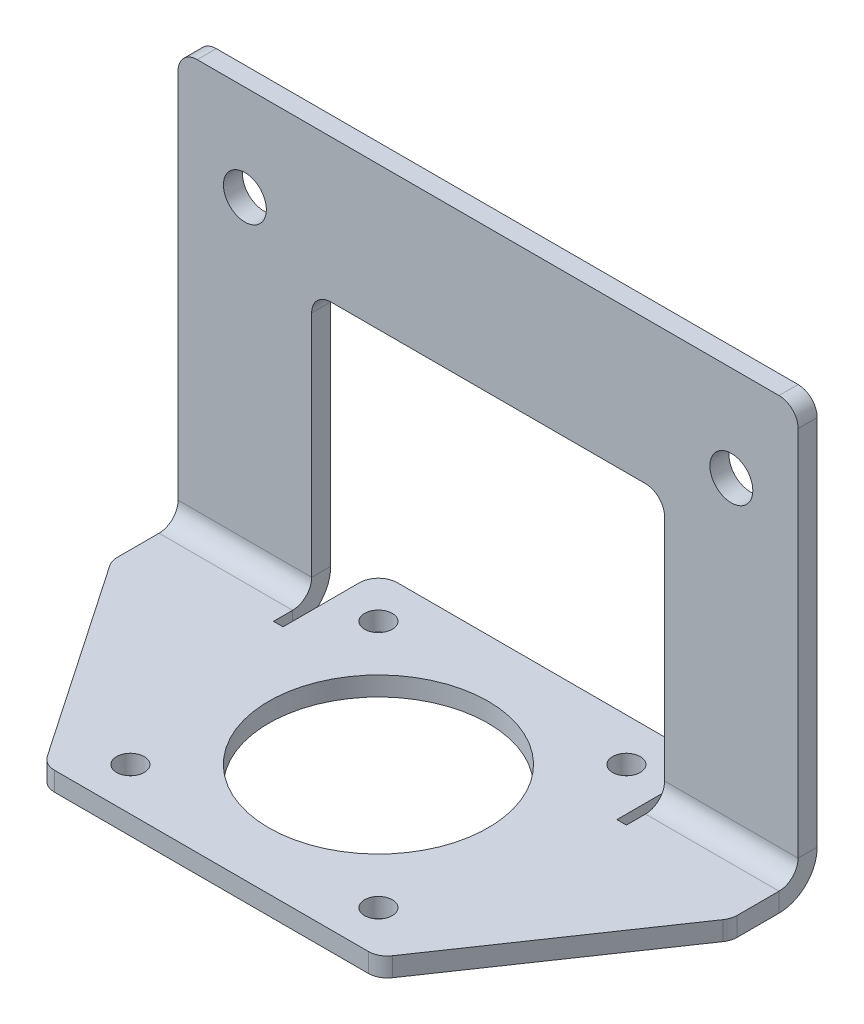
SolidWorks part; units mm, degrees
note: The reader was unsure of these and kept them because the rebuilt part matched: flange length of "Edge-Flange1".
material "Plain Carbon Steel"
ref_plane "Front Plane" through (0, 0, 0) normal (0, 0, 1) x (1, 0, 0)
ref_plane "Top Plane" through (0, 0, 0) normal (0, 1, 0) x (1, 0, 0)
ref_plane "Right Plane" through (0, 0, 0) normal (1, 0, 0) x (0, 0, -1)
sketch "Sketch1" plane through (0, 0, 0) normal (0, 1, 0) x (1, 0, 0)
  line L0 (-17.5, -17.5) -> (-32.5, -17.5)
  line L1 (-17.5, -17.5) -> (17.5, -17.5)
  line L2 (-17.5, 8.5) -> (-17.5, 17.5)
  line L3 (-17.5, 17.5) -> (17.5, 17.5)
  line L4 (17.5, 8.5) -> (17.5, 17.5)
  line L5 (-17.5, -17.5) -> (17.5, 17.5) construction
  line L6 (-17.5, 17.5) -> (17.5, -17.5) construction
  line L7 (-32.5, -17.5) -> (-32.5, 9.5)
  line L8 (-32.5, 9.5) -> (-18.5, 9.5)
  line L9 (0, 0) -> (0, 17.5) construction
  line L10 (17.5, -17.5) -> (32.5, -17.5)
  line L11 (32.5, -17.5) -> (32.5, 9.5)
  line L12 (32.5, 9.5) -> (18.5, 9.5)
  line L13 (-18.5, 9.5) -> (-18.5, 7.5)
  line L14 (-18.5, 7.5) -> (-17.5, 7.5)
  line L15 (-17.5, 7.5) -> (-17.5, 8.5)
  line L16 (17.5, 7.5) -> (17.5, 8.5)
  line L17 (18.5, 7.5) -> (17.5, 7.5)
  line L18 (18.5, 9.5) -> (18.5, 7.5)
  point P0 (0, 0)
  dimension "D1" = 35
  dimension "D2" = 15
  dimension "D3" = 9
  dimension "D4" = 17.5
  dimension "D5" = 17.5
  dimension "D6" = 2
  dimension "D7" = 1
  dimension "D8" = 8
base flange "Base-Flange1" sketch "Sketch1" thickness 2 reverse thickness direction no parameters "D1"=2
edge flange "Edge-Flange1" sketch "Sketch8" flange angle 90 flange length 45 flange position bend outside bend radius 2 thickness 2 relief rectangular parameters "D6"=10
sketch "Sketch8" plane through (0, 0, -9.5) normal (0, 0, -1) x (-1, 0, 0)
  line L0 (18.5, 0) -> (32.5, 0) construction
  line L1 (18.5, 0) -> (32.5, 0)
  line L2 (18.5, 0) -> (18.5, 43)
  line L3 (18.5, 43) -> (32.5, 43)
  line L4 (32.5, 43) -> (32.5, 0)
bend "EdgeBend1" bend radius 2 bend angle 90 parameters "D5"=1
mirror "Mirror1" about plane through (0, 0, 0) normal (1, 0, 0) of "Edge-Flange1"
bend "MirrorBend1" bend radius 2 bend angle 90 parameters "D5"=2
fillet "Fillet1" radius 2 2 edges at (17.5, -1, -17.5) (-17.5, -1, -17.5)
sketch "Sketch9" plane through (0, 0, -11.5) normal (0, 0, 1) x (1, 0, 0)
  line L0 (18.5, 43) -> (18.5, 2) construction
  line L1 (-18.5, 43) -> (18.5, 43)
  line L2 (-18.5, 43) -> (-18.5, 28)
  line L3 (-18.5, 28) -> (18.5, 28)
  line L4 (18.5, 43) -> (18.5, 28)
  line L5 (15.5, 0) -> (-15.5, 0) construction
  dimension "D1" = 28
extrude "Boss-Extrude1" add sketch "Sketch9" against normal blind 2
fillet "Fillet2" radius 2 4 edges at (-18.5, 28, -12.5) (18.5, 28, -12.5) (32.5, 43, -12.5) (-32.5, 43, -12.5)
sketch "Sketch10" plane through (0, 0, 0) normal (0, 1, 0) x (1, 0, 0)
  line L0 (-32.5, 4.5) -> (-17.5, -17.5)
  line L1 (-32.5, 9.5) -> (-32.5, -17.5) construction
  line L2 (-32.5, -17.5) -> (32.5, -17.5) construction
  line L3 (-17.5, -17.5) -> (-32.5, -17.5)
  line L4 (-32.5, -17.5) -> (-32.5, 4.5)
  dimension "D1" = 17.5
  dimension "D2" = 5
extrude "Cut-Extrude1" cut sketch "Sketch10" against normal blind 2 normal cut yes
mirror "Mirror2" about plane through (0, 0, 0) normal (1, 0, 0) of "Cut-Extrude1"
fillet "Fillet3" radius 2 4 edges at (-32.5, -1, -4.5) (-17.5, -1, 17.5) (17.5, -1, 17.5) (32.5, -1, -4.5)
hole_wizard "M2.5 Clearance Hole1" positions "Sketch11" profile "Sketch12" hole size "M2.5" standard "ISO" end condition through all
sketch "Sketch11" plane through (0, 0, 0) normal (0, 1, 0) x (1, 0, 0)
  point P0 (13, -13)
  point P3 (-13, -13)
  point P6 (-13, 13)
  point P9 (13, 13)
sketch "Sketch12" plane through (13, 0, 13) normal (1, 0, 0) x (0, 0, 1)
  line L0 (0, 0) -> (0, 2)
  line L1 (0, 2) -> (1.45, 2)
  line L2 (1.45, 2) -> (1.45, 0)
  line L5 (1.45, 0) -> (0, 0)
  line L11 (0, -6.35) -> (0, 107.95) construction
  dimension "Thru Hole Dia." = 2.9
  dimension "Thru Hole Depth" = 2
hole_wizard "M4 Clearance Hole1" positions "Sketch13" profile "Sketch14" hole size "M4" standard "ISO" end condition through all
sketch "Sketch13" plane through (0, 0, -11.5) normal (0, 0, 1) x (1, 0, 0)
  line L0 (-25.5, 33) -> (0, 33) construction
  line L1 (0, 33) -> (25.5, 33) construction
  line L3 (0, 33) -> (0, 43) construction
  line L4 (-30.5, 43) -> (30.5, 43) construction
  line L6 (0, 33) -> (0, 28) construction
  line L7 (-16.5, 28) -> (16.5, 28) construction
  line L9 (-32.5, 2) -> (-32.5, 41) construction
  point P0 (-25.5, 33)
  point P2 (25.5, 33)
  dimension "D1" = 7
  dimension "D2" = 10
sketch "Sketch14" plane through (-25.5, 33, -11.5) normal (1, 0, 0) x (0, -1, 0)
  line L0 (0, 0) -> (0, 6)
  line L1 (0, 6) -> (2.25, 6)
  line L2 (2.25, 6) -> (2.25, 0)
  line L5 (2.25, 0) -> (0, 0)
  line L11 (0, -6.35) -> (0, 107.95) construction
  dimension "Thru Hole Dia." = 4.5
  dimension "Thru Hole Depth" = 6
sketch "Sketch15" plane through (0, 0, 0) normal (0, 1, 0) x (1, 0, 0)
  circle A0 centre (0, 0) radius 11.5
  dimension "D1" = 23
extrude "Cut-Extrude2" cut sketch "Sketch15" against normal blind 10
sketch "Bend-Lines1" [suppressed] plane through (0, 0, 0) normal (0, 1, 0) x (1, 0, 0)
sketch "Bounding-Box1" [suppressed] plane through (0, 0, 0) normal (0, 1, 0) x (1, 0, 0)
sheet metal parameters "Sheet-Metal1" thickness 2 parameters "D1"=2
flat pattern "Flat-Pattern1" [suppressed]
sketch "Bend-Lines2" plane through (0, 0, 0) normal (0, 1, 0) x (1, 0, 0)
sketch3d "Bounding-Box2" [suppressed]
  line L0 (-17.5, 17.5, 0) -> (32.5, 17.5, 0) construction
  line L1 (-17.5, -17.5, 0) -> (32.5, -17.5, 0) construction
  line L2 (-17.5, 17.5, 0) -> (-17.5, -17.5, 0) construction
  line L3 (32.5, 17.5, 0) -> (32.5, -17.5, 0) construction
sheet metal parameters "Sheet-Metal2" thickness 2 parameters "D1"=2
flat pattern "Flat-Pattern1"
sketch "Bend-Lines2" plane through (0, 0, 0) normal (0, 1, 0) x (1, 0, 0)
  line L0 (-17.5, 15.8562) -> (-32.5, 15.8562) construction
  line L1 (-17.5, 15.8562) -> (-32.5, 15.8562) construction
sketch3d "Bounding-Box2" [suppressed]
  line L0 (-32.5, -17.5, 0) -> (-32.5, 64.2124, 0) construction
  line L1 (32.5, -17.5, 0) -> (32.5, 64.2124, 0) construction
  line L2 (-32.5, -17.5, 0) -> (32.5, -17.5, 0) construction
  line L3 (-32.5, 64.2124, 0) -> (32.5, 64.2124, 0) construction
bend of the flat pattern "Flatten-<EdgeBend1>1"
sheet metal parameters "Sheet-Metal3" thickness 2 parameters "D1"=2
flat pattern "Flat-Pattern1"
sketch "Bend-Lines2" plane through (0, 0, 0) normal (0, 1, 0) x (1, 0, 0)
  line L0 (-18.5, 10.8562) -> (-32.5, 10.8562) construction
  line L1 (-18.5, 10.8562) -> (-32.5, 10.8562) construction
  line L2 (32.5, 10.8562) -> (18.5, 10.8562) construction
  line L3 (32.5, 10.8562) -> (18.5, 10.8562) construction
sketch3d "Bounding-Box2" [suppressed]
  line L0 (-32.5, -17.5, 0) -> (-32.5, 54.2124, 0) construction
  line L1 (32.5, -17.5, 0) -> (32.5, 54.2124, 0) construction
  line L2 (-32.5, -17.5, 0) -> (32.5, -17.5, 0) construction
  line L3 (-32.5, 54.2124, 0) -> (32.5, 54.2124, 0) construction
bend of the flat pattern "Flatten-<EdgeBend1>1"
bend of the flat pattern "Flatten-<MirrorBend1>1"
sheet metal parameters "Sheet-Metal4" thickness 2 parameters "D1"=2
flat pattern "Flat-Pattern1"
sketch "Bend-Lines2" plane through (0, 0, 0) normal (0, 1, 0) x (1, 0, 0)
  line L0 (-18.5, 10.8562) -> (-32.5, 10.8562) construction
  line L1 (-18.5, 10.8562) -> (-32.5, 10.8562) construction
  line L2 (32.5, 10.8562) -> (18.5, 10.8562) construction
  line L3 (32.5, 10.8562) -> (18.5, 10.8562) construction
sketch3d "Bounding-Box2" [suppressed]
  line L0 (-32.5, -17.5, 0) -> (-32.5, 54.2124, 0) construction
  line L1 (32.5, -17.5, 0) -> (32.5, 54.2124, 0) construction
  line L2 (-32.5, -17.5, 0) -> (32.5, -17.5, 0) construction
  line L3 (-32.5, 54.2124, 0) -> (32.5, 54.2124, 0) construction
bend of the flat pattern "Flatten-<EdgeBend1>1"
bend of the flat pattern "Flatten-<MirrorBend1>1"
sheet metal parameters "Sheet-Metal5" thickness 2 parameters "D1"=2
flat pattern "Flat-Pattern1"
sketch "Bend-Lines2" plane through (0, 0, 0) normal (0, 1, 0) x (1, 0, 0)
  line L0 (-18.5, 10.8562) -> (-32.5, 10.8562) construction
  line L1 (-18.5, 10.8562) -> (-32.5, 10.8562) construction
  line L2 (32.5, 10.8562) -> (18.5, 10.8562) construction
  line L3 (32.5, 10.8562) -> (18.5, 10.8562) construction
sketch3d "Bounding-Box2" [suppressed]
  line L0 (-32.5, -17.5, 0) -> (-32.5, 54.2124, 0) construction
  line L1 (32.5, -17.5, 0) -> (32.5, 54.2124, 0) construction
  line L2 (-32.5, -17.5, 0) -> (32.5, -17.5, 0) construction
  line L3 (-32.5, 54.2124, 0) -> (32.5, 54.2124, 0) construction
bend of the flat pattern "Flatten-<EdgeBend1>1"
bend of the flat pattern "Flatten-<MirrorBend1>1"
sheet metal parameters "Sheet-Metal6" thickness 2 parameters "D1"=2
flat pattern "Flat-Pattern1"
sketch "Bend-Lines2" plane through (0, 0, 0) normal (0, 1, 0) x (1, 0, 0)
  line L0 (-18.5, 10.8562) -> (-32.5, 10.8562) construction
  line L1 (-18.5, 10.8562) -> (-32.5, 10.8562) construction
  line L2 (32.5, 10.8562) -> (18.5, 10.8562) construction
  line L3 (32.5, 10.8562) -> (18.5, 10.8562) construction
sketch3d "Bounding-Box2" [suppressed]
  line L0 (-32.5, -17.5, 0) -> (-32.5, 54.2124, 0) construction
  line L1 (32.5, -17.5, 0) -> (32.5, 54.2124, 0) construction
  line L2 (-32.5, -17.5, 0) -> (32.5, -17.5, 0) construction
  line L3 (-32.5, 54.2124, 0) -> (32.5, 54.2124, 0) construction
bend of the flat pattern "Flatten-<EdgeBend1>1"
bend of the flat pattern "Flatten-<MirrorBend1>1"
sheet metal parameters "Sheet-Metal7" thickness 2 parameters "D1"=2
flat pattern "Flat-Pattern1"
sketch "Bend-Lines2" plane through (0, 0, 0) normal (0, 1, 0) x (1, 0, 0)
  line L0 (-18.5, 10.8562) -> (-32.5, 10.8562) construction
  line L1 (-18.5, 10.8562) -> (-32.5, 10.8562) construction
  line L2 (32.5, 10.8562) -> (18.5, 10.8562) construction
  line L3 (32.5, 10.8562) -> (18.5, 10.8562) construction
sketch3d "Bounding-Box2" [suppressed]
  line L0 (-32.5, -17.5, 0) -> (-32.5, 54.2124, 0) construction
  line L1 (32.5, -17.5, 0) -> (32.5, 54.2124, 0) construction
  line L2 (-32.5, -17.5, 0) -> (32.5, -17.5, 0) construction
  line L3 (-32.5, 54.2124, 0) -> (32.5, 54.2124, 0) construction
bend of the flat pattern "Flatten-<EdgeBend1>1"
bend of the flat pattern "Flatten-<MirrorBend1>1"
sheet metal parameters "Sheet-Metal8" thickness 2 parameters "D1"=2
flat pattern "Flat-Pattern1"
sketch "Bend-Lines2" plane through (0, 0, 0) normal (0, 1, 0) x (1, 0, 0)
  line L0 (-18.5, 11.8562) -> (-32.5, 11.8562) construction
  line L1 (-18.5, 11.8562) -> (-32.5, 11.8562) construction
  line L2 (32.5, 11.8562) -> (18.5, 11.8562) construction
  line L3 (32.5, 11.8562) -> (18.5, 11.8562) construction
sketch3d "Bounding-Box2" [suppressed]
  line L0 (-32.5, -17.5, 0) -> (-32.5, 55.2124, 0) construction
  line L1 (32.5, -17.5, 0) -> (32.5, 55.2124, 0) construction
  line L2 (-32.5, -17.5, 0) -> (32.5, -17.5, 0) construction
  line L3 (-32.5, 55.2124, 0) -> (32.5, 55.2124, 0) construction
bend of the flat pattern "Flatten-<EdgeBend1>1"
bend of the flat pattern "Flatten-<MirrorBend1>1"
sheet metal parameters "Sheet-Metal9" thickness 2 parameters "D1"=2
flat pattern "Flat-Pattern1"
sketch "Bend-Lines2" plane through (0, 0, 0) normal (0, 1, 0) x (1, 0, 0)
  line L0 (-18.5, 11.8562) -> (-32.5, 11.8562) construction
  line L1 (-18.5, 11.8562) -> (-32.5, 11.8562) construction
  line L2 (32.5, 11.8562) -> (18.5, 11.8562) construction
  line L3 (32.5, 11.8562) -> (18.5, 11.8562) construction
sketch3d "Bounding-Box2" [suppressed]
  line L0 (-32.5, -17.5, 0) -> (-32.5, 55.2124, 0) construction
  line L1 (32.5, -17.5, 0) -> (32.5, 55.2124, 0) construction
  line L2 (-32.5, -17.5, 0) -> (32.5, -17.5, 0) construction
  line L3 (-32.5, 55.2124, 0) -> (32.5, 55.2124, 0) construction
bend of the flat pattern "Flatten-<EdgeBend1>1"
bend of the flat pattern "Flatten-<MirrorBend1>1"
